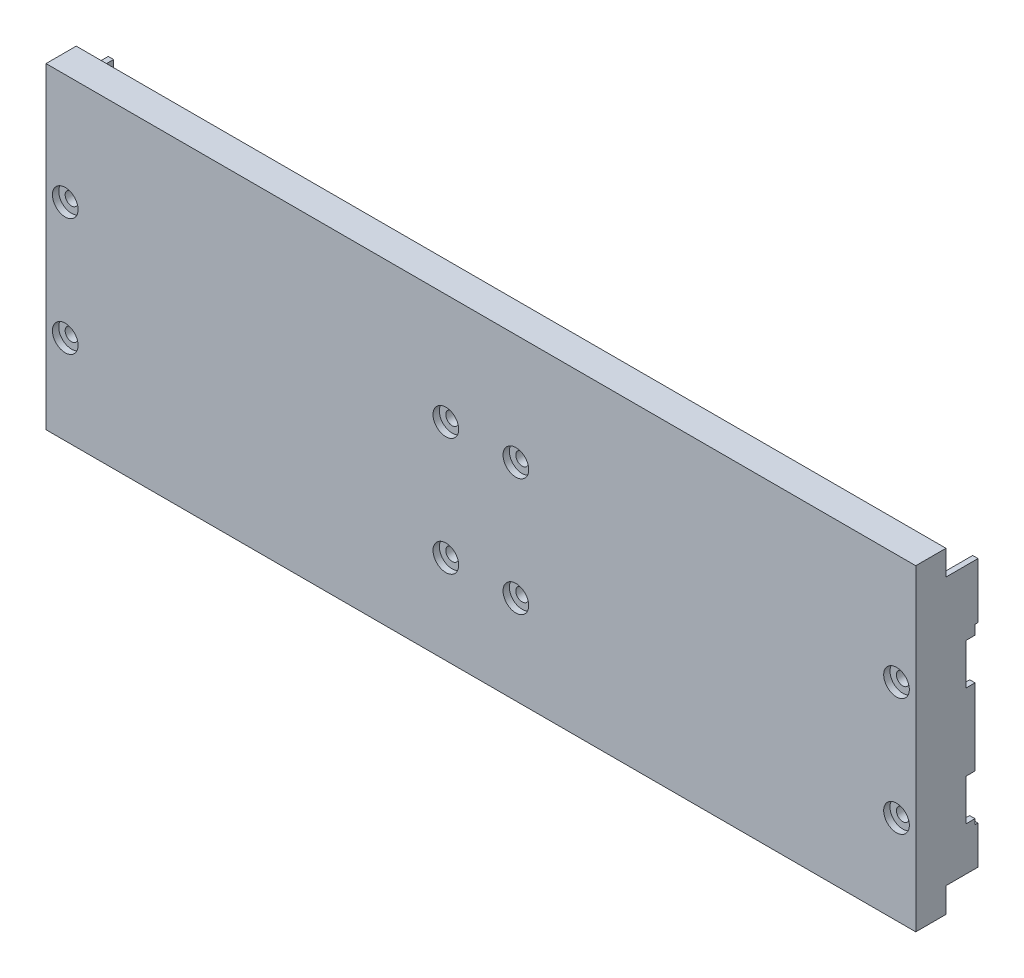
SolidWorks part; units mm, degrees
ref_plane "Front Plane" through (0, 0, 0) normal (0, 0, 1) x (1, 0, 0)
ref_plane "Top Plane" through (0, 0, 0) normal (0, 1, 0) x (1, 0, 0)
ref_plane "Right Plane" through (0, 0, 0) normal (1, 0, 0) x (0, 0, -1)
sketch "Sketch1" plane through (0, 0, 0) normal (0, 0, 1) x (1, 0, 0)
  line L0 (-30.5002, 35.0258) -> (66.0198, 35.0258) construction
  line L1 (67.5438, 35.0258) -> (-139.0852, 35.0258)
  line L2 (67.5438, 35.0258) -> (67.5438, -28.4742)
  line L3 (67.5438, -28.4742) -> (-139.0852, -28.4742)
  line L4 (-139.0852, 35.0258) -> (-139.0852, -28.4742)
  line L5 (66.0198, -28.4742) -> (-30.5002, -28.4742) construction
  line L6 (-137.5612, -28.4742) -> (-137.5612, 35.0258) construction
  line L7 (66.0198, 35.0258) -> (66.0198, -28.4742) construction
  dimension "D1" = 1.524
  dimension "D2" = 1.524
extrude "base" add sketch "Sketch1" along normal blind 5.08
sketch "Sketch2" plane through (0, 0, 0) normal (0, 0, -1) x (-1, 0, 0)
  line L0 (-67.5438, 35.0258) -> (139.0852, 35.0258) construction
  line L1 (137.5612, -26.9502) -> (-66.0198, -26.9502)
  line L2 (137.5612, -26.9502) -> (137.5612, 33.5018)
  line L3 (137.5612, 33.5018) -> (-66.0198, 33.5018)
  line L4 (-66.0198, -26.9502) -> (-66.0198, 33.5018)
  line L5 (-67.5438, -28.4742) -> (-67.5438, 35.0258) construction
  line L6 (139.0852, -28.4742) -> (-67.5438, -28.4742) construction
  line L7 (139.0852, 35.0258) -> (139.0852, -28.4742) construction
  dimension "D1" = 1.524
  dimension "D2" = 1.524
  dimension "D3" = 1.524
  dimension "D4" = 1.524
extrude "hollow" cut sketch "Sketch2" against normal blind 2
sketch "Sketch3" plane through (0, 0, 0) normal (0, 0, -1) x (-1, 0, 0)
  line L0 (-67.5438, 35.0258) -> (139.0852, 35.0258) construction
  line L1 (137.8152, 35.0258) -> (139.0852, 35.0258)
  line L2 (137.8152, 35.0258) -> (137.8152, -28.4742)
  line L3 (137.8152, -28.4742) -> (139.0852, -28.4742)
  line L4 (139.0852, 35.0258) -> (139.0852, -28.4742)
  line L5 (139.0852, -28.4742) -> (-67.5438, -28.4742) construction
  line L7 (139.0852, 35.0258) -> (139.0852, -28.4742) construction
  line L9 (-67.5438, 35.0258) -> (-66.2738, 35.0258)
  line L10 (-67.5438, 35.0258) -> (-67.5438, -28.4742)
  line L11 (-67.5438, -28.4742) -> (-66.2738, -28.4742)
  line L12 (-66.2738, 35.0258) -> (-66.2738, -28.4742)
  dimension "D1" = 1.27
  dimension "D2" = 1.27
extrude "end pieces" add sketch "Sketch3" along normal blind 9
sketch "Sketch7" plane through (67.5438, 0, 0) normal (1, 0, 0) x (0, 0, -1)
  line L0 (9, 35.0258) -> (9, -28.4742) construction
  line L1 (6.7986, 9.8068) -> (9, 9.8068)
  line L2 (6.7986, 9.8068) -> (6.7986, 19.6048)
  line L3 (6.7986, 19.6048) -> (9, 19.6048)
  line L4 (9, 9.8068) -> (9, 19.6048)
  line L5 (6.9986, 19.4048) -> (16.7986, 19.4048) construction
  line L6 (6.9986, 19.4048) -> (6.9986, 10.0068) construction
  line L7 (6.9986, 10.0068) -> (16.7986, 10.0068) construction
  line L8 (6.9986, -17.9332) -> (16.7986, -17.9332) construction
  line L9 (6.7986, -18.1332) -> (9, -18.1332)
  line L10 (6.7986, -18.1332) -> (6.7986, -8.3352)
  line L11 (6.7986, -8.3352) -> (9, -8.3352)
  line L12 (9, -18.1332) -> (9, -8.3352)
  dimension "D1" = 0.2
  dimension "D2" = 0.2
  dimension "D3" = 0.2
  dimension "D4" = 0.2
extrude "where top intrudes" cut sketch "Sketch7" against normal through all
sketch "cable stop wings" [suppressed] plane through (0, 0, 5.08) normal (0, 0, 1) x (1, 0, 0)
  line L0 (-139.0852, 35.0258) -> (-139.0852, -28.4742) construction
  line L1 (-139.0852, -28.4742) -> (67.5438, -28.4742)
  line L2 (-139.0852, -28.4742) -> (-139.0852, -46.2542)
  line L3 (-139.0852, -46.2542) -> (67.5438, -46.2542)
  line L4 (67.5438, -28.4742) -> (67.5438, -46.2542)
  line L5 (67.5438, -28.4742) -> (67.5438, 35.0258) construction
  line L6 (-139.0852, -28.4742) -> (67.5438, -28.4742) construction
  line L8 (-139.0852, 35.0258) -> (67.5438, 35.0258)
  line L9 (-139.0852, 35.0258) -> (-139.0852, 52.8058)
  line L10 (-139.0852, 52.8058) -> (67.5438, 52.8058)
  line L11 (67.5438, 35.0258) -> (67.5438, 52.8058)
  dimension "D1" = 17.78
extrude "cable stop wing boss" [suppressed] add sketch "cable stop wings" against normal blind 1.5 separate body
sketch "cable stop wings alt" plane through (0, 0, 5.08) normal (0, 0, 1) x (1, 0, 0)
  line L1 (-139.0852, -28.4742) -> (67.5438, -28.4742)
  line L2 (-139.0852, -28.4742) -> (-139.0852, -33.4742)
  line L3 (-139.0852, -33.4742) -> (67.5438, -33.4742)
  line L4 (67.5438, -28.4742) -> (67.5438, -33.4742)
  line L5 (67.5438, 35.0258) -> (-139.0852, 35.0258) construction
  line L6 (-139.0852, -28.4742) -> (67.5438, -28.4742) construction
  line L8 (-139.0852, 35.0258) -> (67.5438, 35.0258)
  line L9 (-139.0852, 35.0258) -> (-139.0852, 40.0258)
  line L10 (-139.0852, 40.0258) -> (67.5438, 40.0258)
  line L11 (67.5438, 35.0258) -> (67.5438, 40.0258)
  line L12 (67.5438, -28.4742) -> (67.5438, 35.0258) construction
  line L13 (-139.0852, 35.0258) -> (-139.0852, -28.4742) construction
  dimension "D1" = 5
extrude "cable stop wing boss alt" add sketch "cable stop wings alt" against normal blind 1.5
sketch "Sketch4" plane through (0, 0, 2) normal (0, 0, -1) x (-1, 0, 0)
  circle A0 centre (-62.9718, 14.7058) radius 3.175
  circle A1 centre (-62.9718, -13.2342) radius 3.175
  circle A2 centre (27.4522, -13.2342) radius 3.175
  circle A3 centre (44.0892, -13.2342) radius 3.175
  circle A4 centre (27.4522, 14.7058) radius 3.175
  circle A5 centre (44.0892, 14.7058) radius 3.175
  circle A6 centre (134.5132, 14.7058) radius 3.175
  circle A7 centre (134.5132, -13.2342) radius 3.175
  dimension "D1" = 6.35
extrude "screw bosses" add sketch "Sketch4" along normal up to surface (2 mm away) up to face at (-35.7707, 3.2758, 0)
sketch "Sketch5" plane through (0, 0, 0) normal (0, 0, -1) x (-1, 0, 0)
  circle A0 centre (-62.9718, 14.7058) radius 1.524
  circle A1 centre (-62.9718, -13.2342) radius 1.524
  circle A2 centre (27.4522, 14.7058) radius 1.524
  circle A3 centre (27.4522, -13.2342) radius 1.524
  circle A4 centre (44.0892, -13.2342) radius 1.524
  circle A5 centre (134.5132, 14.7058) radius 1.524
  circle A6 centre (134.5132, -13.2342) radius 1.524
  circle A7 centre (44.0892, 14.7058) radius 1.524
  dimension "D1" = 3.048
extrude "screw holes" cut sketch "Sketch5" against normal through all
sketch "wing extensions" [suppressed] plane through (0, 0, 5.08) normal (0, 0, -1) x (-1, 0, 0)
  line L0 (136.3082, -28.3942) -> (136.3082, -19.3942) construction
  line L1 (-73.6398, 52.8058) -> (-66.2908, 52.8058)
  line L2 (-73.6398, 52.8058) -> (-73.6398, 35.0258)
  line L3 (-73.6398, 35.0258) -> (-66.2908, 35.0258)
  line L4 (145.1812, 52.8058) -> (145.1812, 35.0258)
  line L6 (137.5612, -26.9502) -> (137.5612, 33.5018) construction
  line L7 (-66.2738, 35.0258) -> (137.8152, 35.0258) construction
  line L8 (-66.2908, -46.2542) -> (137.8322, -46.2542) construction
  line L10 (39.4452, -28.4742) -> (32.0962, -28.4742)
  line L11 (39.4452, -28.4742) -> (39.4452, -46.2542)
  line L12 (-73.6398, -46.2542) -> (-66.2908, -46.2542)
  line L13 (-73.6398, -46.2542) -> (-73.6398, -28.4742)
  line L14 (-73.6398, -28.4742) -> (-66.2908, -28.4742)
  line L15 (145.1812, -46.2542) -> (145.1812, -28.4742)
  line L16 (39.4452, -46.2542) -> (32.0962, -46.2542)
  line L17 (32.0962, -28.4742) -> (32.0962, -46.2542)
  line L18 (-66.0198, 33.5018) -> (-66.0198, -26.9502) construction
  line L19 (139.0852, -46.2542) -> (-67.5438, -46.2542) construction
  line L20 (137.8322, 35.0258) -> (137.8322, 52.8058)
  line L21 (-66.2908, 35.0258) -> (-66.2908, 52.8058)
  line L22 (-66.2908, -28.4742) -> (-66.2908, -46.2542)
  line L23 (137.8322, -28.4742) -> (137.8322, -46.2542)
  line L24 (137.8322, -46.2542) -> (145.1812, -46.2542)
  line L25 (137.8322, -28.4742) -> (145.1812, -28.4742)
  line L26 (137.8322, 52.8058) -> (145.1812, 52.8058)
  line L27 (137.8322, 35.0258) -> (145.1812, 35.0258)
  line L28 (39.4452, -28.4742) -> (32.0962, -46.2542) construction
  line L29 (39.4452, -46.2542) -> (32.0962, -28.4742) construction
  line L30 (139.0852, -28.4742) -> (-67.5438, -28.4742) construction
  line L31 (-67.5438, 35.0258) -> (139.0852, 35.0258) construction
  line L32 (32.0962, 52.8058) -> (39.4452, 52.8058)
  line L38 (32.0962, 52.8058) -> (32.0962, 35.0258)
  line L39 (32.0962, 35.0258) -> (39.4452, 35.0258)
  line L46 (39.4452, 52.8058) -> (39.4452, 35.0258)
  point P30 (35.7707, -37.3642)
  point P37 (35.7707, -46.2542)
  dimension "D1" = 7.62
  dimension "D2" = 7.62
  dimension "D3" = 1.524
extrude "wingtip risers" [suppressed] add sketch "wing extensions" along normal blind 7.874
ref_point "Point1" [suppressed]
ref_point "Point2" [suppressed]
ref_point "Point3" [suppressed]
ref_point "Point4" [suppressed]
ref_axis "Axis1" [suppressed] through (69.9653, 43.9158, -2.794) along (-1, 0, 0)
ref_axis "Axis2" [suppressed] through (69.9653, -37.3642, -2.794) along (-1, 0, 0)
sketch "Sketch10" [suppressed] plane through (0, 0, -2.794) normal (0, 0, -1) x (-1, 0, 0)
  line L0 (-66.2908, 52.8058) -> (-73.6398, 52.8058) construction
  line L1 (145.1812, 52.8058) -> (137.8322, 52.8058) construction
  line L3 (-73.6398, 35.0258) -> (-66.2908, 35.0258) construction
  line L4 (-73.6398, 52.8058) -> (-73.6398, 35.0258) construction
  line L5 (-66.2908, 35.0258) -> (-66.2908, 52.8058) construction
  line L6 (32.0962, 35.0258) -> (39.4452, 35.0258) construction
  circle A0 centre (-69.9653, 50.5198) radius 1.8288
  circle A1 centre (141.5067, 50.5198) radius 1.8288
  circle A2 centre (35.7707, 50.5198) radius 1.8288
  point P5 (-69.9653, 52.8058)
  point P10 (141.5067, 52.8058)
  point P21 (-69.9653, 35.0258)
  point P24 (35.7707, 35.0258)
  dimension "D1" = 3.6576
  dimension "D2" = 2.286
revolve "cable retention tunnel 1" [suppressed] cut sketch "Sketch10" angle 180 about axis through (69.9653, 43.9158, -2.794) along (-1, 0, 0) reverse direction yes
sketch "Sketch11" [suppressed] plane through (0, 0, -2.794) normal (0, 0, -1) x (-1, 0, 0)
  line L0 (-67.5438, -28.4742) -> (-73.6398, -28.4742) construction
  line L2 (137.8322, -46.2542) -> (145.1812, -46.2542) construction
  line L3 (-73.6398, -46.2542) -> (-66.2908, -46.2542) construction
  line L5 (32.0962, -46.2542) -> (39.4452, -46.2542) construction
  circle A0 centre (-69.9653, -30.7602) radius 1.8288
  circle A1 centre (35.7707, -30.7602) radius 1.8288
  circle A2 centre (141.5067, -30.7602) radius 1.8288
  circle A3 centre (-69.9653, 37.3118) radius 1.8288 construction
  point P18 (141.5067, -46.2542)
  point P22 (-69.9653, -46.2542)
  point P24 (35.7707, -46.2542)
  dimension "D1" = 2.286
revolve "cable retention tunnel 2" [suppressed] cut sketch "Sketch11" angle 180 about axis through (69.9653, -37.3642, -2.794) along (-1, 0, 0) reverse direction yes
fillet "Fillet1" [suppressed] radius 0.889
sketch "Sketch12" [suppressed] plane through (0, 0, 5.08) normal (0, 0, 1) x (1, 0, 0)
  line L0 (-145.1812, 52.8058) -> (73.6398, 52.8058) construction
  line L1 (-145.1812, 35.0258) -> (-145.1812, 52.8058) construction
  line L3 (-145.1812, -46.2542) -> (73.6398, -46.2542) construction
  line L4 (58.3998, 47.7258) -> (73.6398, 47.7258) construction
  line L5 (73.6398, 52.8058) -> (73.6398, 35.0258) construction
  line L6 (-129.9412, 47.7258) -> (-145.1812, 47.7258) construction
  line L7 (-145.1812, 35.0258) -> (-145.1812, 52.8058) construction
  circle A0 centre (-129.9412, 47.7258) radius 2.032
  circle A1 centre (-129.9412, 40.1058) radius 2.032
  circle A2 centre (-129.9412, -33.5542) radius 2.032
  circle A3 centre (-129.9412, -41.1742) radius 2.032
  circle A4 centre (58.3998, -41.1742) radius 2.032
  circle A5 centre (58.3998, -33.5542) radius 2.032
  circle A6 centre (58.3998, 40.1058) radius 2.032
  circle A7 centre (58.3998, 47.7258) radius 2.032
  dimension "D1" = 4.064
  dimension "D2" = 12.7
  dimension "D3" = 5.08
  dimension "D4" = 15.24
  dimension "D6" = 5.08
  dimension "D7" = 12.7
extrude "screw holes on wings" [suppressed] cut sketch "Sketch12" against normal through all
sketch "Sketch6" plane through (0, 0, 5.08) normal (0, 0, 1) x (1, 0, 0)
  circle A0 centre (62.9718, -13.2342) radius 3.048
  circle A1 centre (62.9718, 14.7058) radius 3.048
  circle A2 centre (-27.4522, -13.2342) radius 3.048
  circle A3 centre (-44.0892, -13.2342) radius 3.048
  circle A4 centre (-27.4522, 14.7058) radius 3.048
  circle A5 centre (-44.0892, 14.7058) radius 3.048
  circle A6 centre (-134.5132, 14.7058) radius 3.048
  circle A7 centre (-134.5132, -13.2342) radius 3.048
  dimension "D1" = 6.096
extrude "counter sink" cut sketch "Sketch6" against normal blind 1.5
sketch "Sketch13" [suppressed] plane through (-145.1812, 0, 0) normal (-1, 0, 0) x (0, 0, 1)
  line L0 (-2.794, -46.2542) -> (-2.794, -28.4742) construction
  line L1 (-2.794, 35.0258) -> (-2.794, 52.8058) construction
  circle A0 centre (-2.794, -37.3642) radius 4.191
  circle A1 centre (-2.794, 43.9158) radius 4.191
  dimension "D1" = 8.382
extrude "cable hollow" [suppressed] cut sketch "Sketch13" against normal through all
sketch "Sketch14" plane through (0, 0, 5.08) normal (0, 0, 1) x (1, 0, 0)
  line L5 (35.9798, 34.9458) -> (65.9798, 34.9458) construction
  line L6 (59.8698, 34.9458) -> (42.0898, 34.9458)
  line L7 (59.8698, 34.9458) -> (59.8698, 40.0258)
  line L8 (59.8698, 40.0258) -> (42.0898, 40.0258)
  line L9 (42.0898, 34.9458) -> (42.0898, 40.0258)
  line L10 (59.8698, 34.9458) -> (42.0898, 40.0258) construction
  line L11 (59.8698, 40.0258) -> (42.0898, 34.9458) construction
  line L12 (33.5728, 34.9458) -> (3.5728, 34.9458) construction
  line L13 (1.4638, 34.9458) -> (-28.5362, 34.9458) construction
  line L15 (-22.4262, 40.0258) -> (-4.6462, 40.0258)
  line L16 (-22.4262, 40.0258) -> (-22.4262, 34.9458)
  line L17 (-22.4262, 34.9458) -> (-4.6462, 34.9458)
  line L18 (-4.6462, 40.0258) -> (-4.6462, 34.9458)
  line L19 (-22.4262, 40.0258) -> (-4.6462, 34.9458) construction
  line L20 (-22.4262, 34.9458) -> (-4.6462, 40.0258) construction
  line L21 (9.6828, 34.9458) -> (27.4628, 34.9458)
  line L22 (9.6828, 34.9458) -> (9.6828, 40.0258)
  line L23 (9.6828, 40.0258) -> (27.4628, 40.0258)
  line L24 (27.4628, 34.9458) -> (27.4628, 40.0258)
  line L25 (9.6828, 34.9458) -> (27.4628, 40.0258) construction
  line L26 (9.6828, 40.0258) -> (27.4628, 34.9458) construction
  line L27 (67.5438, 40.0258) -> (-139.0852, 40.0258) construction
  point P0 (50.9798, 37.4858)
  point P7 (50.9798, 34.9458)
  point P18 (-13.5362, 37.4858)
  point P23 (18.5728, 37.4858)
  point P28 (18.5728, 34.9458)
  point P29 (-13.5362, 34.9458)
  dimension "D1" = 17.78
  dimension "D2" = 5.08
extrude "anchors-output" [suppressed] add sketch "Sketch14" against normal blind 7.62
sketch "Sketch15" plane through (0, 0, 5.08) normal (0, 0, -1) x (-1, 0, 0)
  line L0 (-65.5698, -28.3942) -> (-35.5698, -28.3942) construction
  line L1 (-59.4598, -28.3942) -> (-41.6798, -28.3942)
  line L2 (-59.4598, -28.3942) -> (-59.4598, -33.4742)
  line L3 (-59.4598, -33.4742) -> (-41.6798, -33.4742)
  line L4 (-41.6798, -28.3942) -> (-41.6798, -33.4742)
  line L5 (-59.4598, -28.3942) -> (-41.6798, -33.4742) construction
  line L6 (-59.4598, -33.4742) -> (-41.6798, -28.3942) construction
  line L7 (-27.0528, -28.3942) -> (-9.2728, -28.3942)
  line L8 (-27.0528, -28.3942) -> (-27.0528, -33.4742)
  line L9 (-27.0528, -33.4742) -> (-9.2728, -33.4742)
  line L10 (-9.2728, -28.3942) -> (-9.2728, -33.4742)
  line L11 (-27.0528, -28.3942) -> (-9.2728, -33.4742) construction
  line L12 (-27.0528, -33.4742) -> (-9.2728, -28.3942) construction
  line L13 (5.3572, -28.3942) -> (23.1372, -28.3942)
  line L14 (5.3572, -28.3942) -> (5.3572, -33.4742)
  line L15 (5.3572, -33.4742) -> (23.1372, -33.4742)
  line L16 (23.1372, -28.3942) -> (23.1372, -33.4742)
  line L17 (5.3572, -28.3942) -> (23.1372, -33.4742) construction
  line L18 (5.3572, -33.4742) -> (23.1372, -28.3942) construction
  line L19 (-33.1628, -28.3942) -> (-3.1628, -28.3942) construction
  line L20 (-0.7528, -28.3942) -> (29.2472, -28.3942) construction
  line L21 (139.0852, -33.4742) -> (-67.5438, -33.4742) construction
  point P0 (-50.5698, -30.9342)
  point P5 (-18.1628, -30.9342)
  point P10 (14.2472, -30.9342)
  point P19 (-50.5698, -28.3942)
  point P24 (-18.1628, -28.3942)
  point P29 (14.2472, -28.3942)
  dimension "D1" = 5.08
  dimension "D2" = 17.78
extrude "anchors-input" [suppressed] add sketch "Sketch15" along normal blind 7.62
ref_point "anchor out 1 center" [suppressed]
ref_point "anchor out 2 center" [suppressed]
ref_point "anchor out 3 center" [suppressed]
ref_axis "anchor out 1 axis" [suppressed] through (50.9798, 54.0758, -2.54) along (0, 1, 0)
ref_axis "anchor out 2 axis" [suppressed] through (18.5728, 54.0758, -2.54) along (0, 1, 0)
ref_axis "anchor out 3 axis" [suppressed] through (-13.5362, 54.0758, -2.54) along (0, 1, 0)
sketch "Sketch16" [suppressed] plane through (0, 0, -2.54) normal (0, 0, -1) x (-1, 0, 0)
  line L0 (-59.8698, 51.5358) -> (-59.8698, 56.6158) construction
  circle A0 centre (-57.3298, 54.0758) radius 1.778
  point P4 (-59.8698, 54.0758)
  dimension "D1" = 3.556
  dimension "D2" = 2.54
revolve "anchor 1 out cut" [suppressed] cut sketch "Sketch16" angle 180 about axis through (50.9798, 54.0758, -2.54) along (0, 1, 0) reverse direction yes
sketch "Sketch17" [suppressed] plane through (0, 0, -2.54) normal (0, 0, -1) x (-1, 0, 0)
  line L1 (-27.4628, 51.5358) -> (-27.4628, 56.6158) construction
  circle A0 centre (-24.9228, 54.0758) radius 1.778
  point P5 (-27.4628, 54.0758)
  dimension "D1" = 3.556
  dimension "D2" = 2.54
revolve "anchor 2 out cut" [suppressed] cut sketch "Sketch17" angle 180 about axis through (18.5728, 54.0758, -2.54) along (0, 1, 0) reverse direction yes
sketch "Sketch18" [suppressed] plane through (0, 0, -2.54) normal (0, 0, -1) x (-1, 0, 0)
  line L0 (4.6462, 51.5358) -> (4.6462, 56.6158) construction
  circle A0 centre (7.1862, 54.0758) radius 1.778
  point P5 (4.6462, 54.0758)
  dimension "D2" = 3.556
  dimension "D1" = 2.54
revolve "anchor 3 out cut" [suppressed] cut sketch "Sketch18" angle 180 about axis through (-13.5362, 54.0758, -2.54) along (0, 1, 0) reverse direction yes
sketch "Sketch20" [suppressed] plane through (0, 51.5358, 0) normal (0, -1, 0) x (1, 0, 0)
  circle A0 centre (50.9798, -2.54) radius 3.81
  circle A1 centre (18.5728, -2.54) radius 3.81
  circle A2 centre (-13.5362, -2.54) radius 3.81
  dimension "D1" = 7.62
extrude "cable hollow alt out" [suppressed] cut sketch "Sketch20" against normal through all
ref_point "anchor in 1 center" [suppressed]
ref_point "anchor in 2 center" [suppressed]
ref_point "anchor in 3 center" [suppressed]
ref_axis "anchor in 1 axis" [suppressed] through (50.5698, -46.2542, -2.54) along (0, -1, 0)
ref_axis "anchor in 2 axis" [suppressed] through (18.1628, -46.2542, -2.54) along (0, -1, 0)
ref_axis "anchor in 3 axis" [suppressed] through (-14.2472, -46.2542, -2.54) along (0, -1, 0)
sketch "Sketch19" [suppressed] plane through (0, 0, -2.54) normal (0, 0, -1) x (-1, 0, 0)
  line L0 (-59.4598, -43.7142) -> (-59.4598, -48.7942) construction
  circle A0 centre (-56.9198, -46.2542) radius 1.778
  point P4 (-59.4598, -46.2542)
  dimension "D2" = 3.556
  dimension "D1" = 2.54
revolve "anchor 1 in cut" [suppressed] cut sketch "Sketch19" angle 180 about axis through (50.5698, -46.2542, -2.54) along (0, -1, 0)
sketch "Sketch21" [suppressed] plane through (0, 0, -2.54) normal (0, 0, -1) x (-1, 0, 0)
  line L0 (-27.0528, -43.7142) -> (-27.0528, -48.7942) construction
  line L1 (-27.0528, -43.7142) -> (-27.0528, -48.7942) construction
  circle A0 centre (-24.5128, -46.2542) radius 1.778
  point P4 (-27.0528, -46.2542)
  dimension "D2" = 3.556
  dimension "D1" = 2.54
revolve "anchor 2 in cut" [suppressed] cut sketch "Sketch21" angle 180 about axis through (18.1628, -46.2542, -2.54) along (0, -1, 0)
sketch "Sketch22" [suppressed] plane through (0, 0, -2.54) normal (0, 0, -1) x (-1, 0, 0)
  line L0 (5.3572, -43.7142) -> (5.3572, -48.7942) construction
  circle A0 centre (7.8972, -46.2542) radius 1.778
  point P4 (5.3572, -46.2542)
  dimension "D2" = 3.556
  dimension "D1" = 2.54
revolve "anchor 3 in cut" [suppressed] cut sketch "Sketch22" angle 180 about axis through (-14.2472, -46.2542, -2.54) along (0, -1, 0)
sketch "Sketch23" [suppressed] plane through (0, -43.7142, 0) normal (0, 1, 0) x (1, 0, 0)
  circle A0 centre (-14.2472, 2.54) radius 3.81
  circle A1 centre (18.1628, 2.54) radius 3.81
  circle A2 centre (50.5698, 2.54) radius 3.81
  dimension "D1" = 7.62
extrude "cable hollow alt in" [suppressed] cut sketch "Sketch23" against normal through all
pattern_linear "LPattern1" [suppressed] count 2 spacing 106.9975 of bodies 129
sketch "Sketch24" [suppressed] plane through (0, 0, 5.08) normal (0, 0, 1) x (1, 0, 0)
  line L0 (67.5438, -28.4742) -> (59.4598, -48.7942)
  line L1 (59.4598, -48.7942) -> (67.5438, -48.7942)
  line L2 (67.5438, -48.7942) -> (67.5438, -28.4742)
  line L3 (59.8698, 56.6158) -> (67.5438, 35.0258)
  line L4 (67.5438, 35.0258) -> (67.5438, 56.6158)
  line L5 (67.5438, 56.6158) -> (59.8698, 56.6158)
  line L7 (-139.0852, 35.0258) -> (-129.4237, 56.6158)
  line L8 (-129.4237, 56.6158) -> (-139.0852, 56.6158)
  line L9 (-139.0852, 56.6158) -> (-139.0852, 35.0258)
  line L10 (-139.0852, -28.4742) -> (-130.1347, -48.7942)
  line L11 (-130.1347, -48.7942) -> (-139.0852, -48.7942)
  line L12 (-139.0852, -48.7942) -> (-139.0852, -28.4742)
extrude "remove corners" [suppressed] cut sketch "Sketch24" against normal through all both and the other way through all
sketch "Sketch25" plane through (0, 0, 5.08) normal (0, 0, 1) x (1, 0, 0)
  line L0 (-105.8162, 35.9458) -> (-135.1786, 35.9458) construction
  line L1 (-139.0852, 40.9458) -> (67.5438, 40.9458)
  line L2 (-139.0852, 40.9458) -> (-139.0852, 36.4458)
  line L3 (-139.0852, 36.4458) -> (67.5438, 36.4458)
  line L4 (67.5438, 40.9458) -> (67.5438, 36.4458)
  line L7 (67.5438, -34.3942) -> (-139.0852, -34.3942)
  line L8 (67.5438, -34.3942) -> (67.5438, -29.8942)
  line L9 (67.5438, -29.8942) -> (-139.0852, -29.8942)
  line L10 (-139.0852, -34.3942) -> (-139.0852, -29.8942)
  line L13 (-139.0852, 40.0258) -> (-139.0852, -33.4742) construction
  line L14 (67.5438, -33.4742) -> (67.5438, 40.0258) construction
  line L15 (-135.5901, -29.3942) -> (-106.2277, -29.3942) construction
  dimension "D1" = 0.5
  dimension "D2" = 5
  dimension "D3" = 0.5
  dimension "D4" = 5
extrude "box under connectors" add sketch "Sketch25" against normal offset from surface (7.1786 mm away) 3.81
sketch "Sketch26" plane through (-139.0852, 0, 0) normal (-1, 0, 0) x (0, 0, 1)
  line L0 (-2.0986, 40.9458) -> (5.08, 40.9458) construction
  line L1 (-2.0986, -34.3942) -> (5.08, -34.3942)
  line L2 (-2.0986, -34.3942) -> (-2.0986, 40.9458)
  line L3 (-2.0986, 40.9458) -> (5.08, 40.9458)
  line L4 (5.08, -34.3942) -> (5.08, 40.9458)
  line L5 (-2.0986, -34.3942) -> (5.08, -34.3942) construction
extrude "Fill ends" add sketch "Sketch26" against normal blind 1.5
extrude "Fill the other end" add sketch "Sketch26<2>" along normal blind 1.5 from surface starting at face at (67.5438, 2.2598, -3.2554)
sketch "Sketch26<2>" plane through (-139.0852, 0, 0) normal (-1, 0, 0) x (0, 0, 1) same geometry as "Sketch26"
sketch "Sketch27" plane through (-139.0852, 0, 0) normal (-1, 0, 0) x (0, 0, 1)
  line L0 (-10.2086, -28.4742) -> (-10.2086, -18.8862) construction
  line L1 (-9, -28.4742) -> (-9.7086, -28.4742)
  line L2 (-9, -28.4742) -> (-9, -19.3862)
  line L3 (-9, -19.3862) -> (-9.7086, -19.3862)
  line L4 (-9.7086, -28.4742) -> (-9.7086, -19.3862)
  line L5 (-9, -18.8862) -> (-10.2086, -18.8862) construction
  line L6 (-9, 21.3568) -> (-10.2086, 21.3568) construction
  line L7 (-9, 35.0258) -> (-9.7086, 35.0258)
  line L8 (-9, 35.0258) -> (-9, 21.8568)
  line L9 (-9, 21.8568) -> (-9.7086, 21.8568)
  line L10 (-9.7086, 35.0258) -> (-9.7086, 21.8568)
  line L11 (-10.2086, 21.3568) -> (-10.2086, 35.0258) construction
  dimension "D1" = 0.5
  dimension "D2" = 0.5
  dimension "D3" = 0.5
  dimension "D4" = 0.5
extrude "Boss-Extrude4" add sketch "Sketch27" against normal up to vertex (1.27 mm away) up to point (-137.8152, 35.0258, -9)
extrude "Boss-Extrude5" add sketch "Sketch27<2>" along normal up to vertex (-205.359 mm away) from surface up to point (66.2738, 35.0258, -9) starting at face at (67.5438, 2.0058, -4.9643)
sketch "Sketch27<2>" plane through (-139.0852, 0, 0) normal (-1, 0, 0) x (0, 0, 1) same geometry as "Sketch27"
